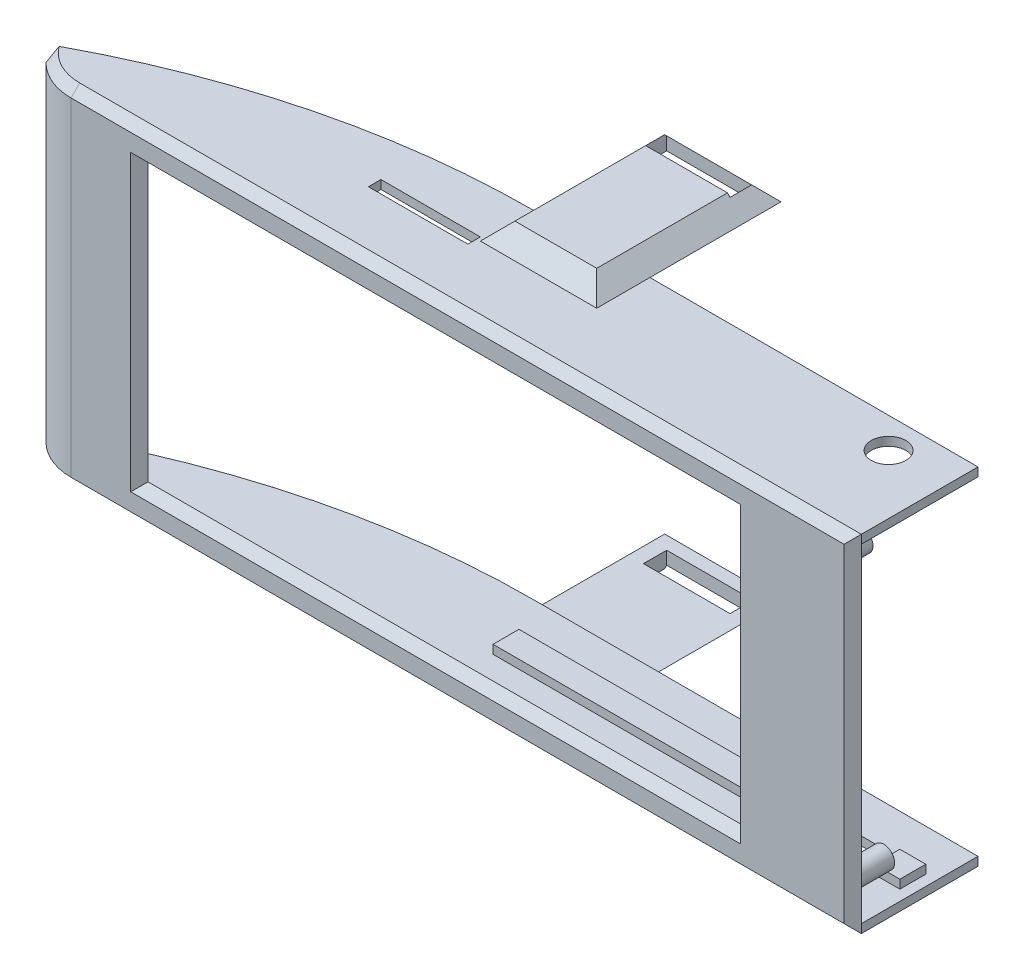
SolidWorks part; units mm, degrees
material "PLA"
ref_plane "Front Plane" through (0, 0, 0) normal (0, 0, 1) x (1, 0, 0)
ref_plane "Top Plane" through (0, 0, 0) normal (0, 1, 0) x (1, 0, 0)
ref_plane "Right Plane" through (0, 0, 0) normal (1, 0, 0) x (0, 0, -1)
sketch "Sketch1" plane through (101441.594, 0, 0) normal (0, 0, 1) x (-1, 0, 0)
  line L1 (101382.549, 35) -> (101451.049, 35)
  line L2 (101382.549, 35) -> (101382.549, 3)
  line L3 (101382.549, 3) -> (101451.049, 3)
  line L8 (101458.949, 39) -> (101368.549, 39)
  line L9 (101458.949, -1) -> (101458.949, 39)
  line L10 (101368.549, -1) -> (101458.949, -1)
  line L11 (101368.549, 39) -> (101368.549, -1)
  line L12 (101451.049, 35) -> (101451.049, 3)
  dimension "D2" = 68.5
  dimension "D3" = 14
  dimension "D4" = 4
  dimension "D5" = 4
  dimension "D6" = 90.4
  dimension "D1" = 40
extrude "Boss-Extrude1" add sketch "Sketch1" along normal blind 1
sketch "Sketch2" plane through (0, 0, 0) normal (0, 0, -1) x (-1, 0, 0)
  line L0 (-73.0451, 1) -> (17.3549, 1) construction
  line L1 (17.3549, -39) -> (-73.0451, -39) construction
  line L2 (-73.0451, -39) -> (-73.0451, 1) construction
  circle A0 centre (-70.1451, -2.5) radius 1.25
  circle A1 centre (-70.1451, -35.5) radius 1.25
  circle A2 centre (14.3549, -2.5) radius 1.25
  circle A3 centre (14.3549, -35.5) radius 1.25
  dimension "D4" = 2.5
  dimension "D1" = 3.5
  dimension "D2" = 3.5
  dimension "D3" = 2.9
  dimension "D5" = 2
extrude "Boss-Extrude2" add sketch "Sketch2" along normal blind 3
sketch "Sketch3" plane through (0, 1, 0) normal (0, 1, 0) x (1, 0, 0)
  line L0 (73.0451, 0) -> (-17.3549, 0) construction
  line L1 (-17.3549, -1) -> (-17.3549, 0) construction
  line L2 (-22.3549, 2.6834) -> (-22.3549, 1.101)
  line L3 (-17.3549, -1) -> (-17.3549, 0)
  arc A0 (-17.3549, 0) -> (-22.3549, 2.6834) centre (-17.3549, 6) cw
  arc A1 (-17.3549, -1) -> (-22.3549, 1.101) centre (-17.3549, 6) cw
  arc A3 (-17.3549, -1) -> (-23.1883, 2.1306) centre (-17.3549, 6) cw construction
  dimension "D1" = 6
  dimension "D2" = 5
extrude "Boss-Extrude3" add sketch "Sketch3" against normal through all separate body
chamfer "Chamfer1" distance 1 angle 45 2 edges at (-20.0667, 1, 0.4534) (-20.0667, -39, 0.4534)
chamfer "Chamfer2" distance 1 angle 45 7 edges at (24.7951, -3, 1) (-9.4549, -19, 1) (24.7951, -35, 1) (59.0451, -19, 1) (27.8451, -39, 1) (73.0451, -19, 1) (27.8451, 1, 1)
ref_plane "Plane1" through (0, -39, 0) normal (0, 1, 0) x (1, 0, 0)
ref_plane "Plane2" through (0, 1, 0) normal (0, 1, 0) x (1, 0, 0)
sketch "Sketch6" plane through (0, 1, 0) normal (0, 1, 0) x (1, 0, 0)
  line L0 (73.0451, 0) -> (-17.3549, 0) construction
  line L1 (71.8188, 0) -> (61.8388, 0)
  line L2 (71.8188, 0) -> (71.8188, 13.9185)
  line L3 (71.8188, 13.9185) -> (61.8388, 13.9185)
  line L4 (61.8388, 0) -> (61.8388, 13.9185)
  line L5 (29.764, 0) -> (-0.962, 0)
  line L6 (29.764, 0) -> (29.764, 11.5588)
  line L7 (29.764, 11.5588) -> (-0.962, 11.5588)
  line L8 (-0.962, 0) -> (-0.962, 11.5588)
  line L10 (19.6612, 5.9892) -> (7.4739, 5.9892)
  line L11 (19.6612, 5.9892) -> (19.6612, 7.9655)
  line L12 (19.6612, 7.9655) -> (7.4739, 7.9655)
  line L13 (7.4739, 5.9892) -> (7.4739, 7.9655)
  circle A0 centre (66.8561, 9.9375) radius 1.9758
extrude "Boss-Extrude4" add sketch "Sketch6" against normal blind 1
sketch "Sketch8" plane through (0, 0, 0) normal (0, -1, 0) x (1, 0, 0)
  line L0 (29.764, 0) -> (29.764, -11.5588) construction
  line L1 (29.764, -8.6788) -> (24.764, -8.6788)
  line L2 (29.764, -8.6788) -> (29.764, -5.6788)
  line L3 (29.764, -5.6788) -> (24.764, -5.6788)
  line L4 (24.764, -8.6788) -> (24.764, -5.6788)
  line L5 (29.764, -11.5588) -> (-0.962, -11.5588) construction
  dimension "D1" = 5.88
  dimension "D2" = 3
  dimension "D3" = 5
extrude "Boss-Extrude6" add sketch "Sketch8" along normal blind 1
sketch "Sketch9" plane through (0, -39, 0) normal (0, 1, 0) x (1, 0, 0)
  line L1 (67.2061, 8.8062) -> (63.1589, 8.8062)
  line L2 (67.2061, 8.8062) -> (67.2061, 6.8122)
  line L3 (67.2061, 6.8122) -> (63.1589, 6.8122)
  line L4 (29.764, 0) -> (29.764, 11.5588)
  line L5 (29.764, 11.5588) -> (-0.962, 11.5588)
  line L6 (-0.962, 11.5588) -> (-0.962, 0)
  line L7 (-0.962, 0) -> (29.764, 0)
  line L8 (29.764, 0) -> (29.764, 11.5588)
  line L9 (29.764, 11.5588) -> (-0.962, 11.5588)
  line L10 (-0.962, 11.5588) -> (-0.962, 0)
  line L11 (-0.962, 0) -> (29.764, 0)
  line L12 (71.8188, 0) -> (71.8188, 13.9185)
  line L13 (61.8388, 0) -> (71.8188, 0)
  line L14 (61.8388, 13.9185) -> (61.8388, 0)
  line L15 (71.8188, 13.9185) -> (61.8388, 13.9185)
  line L16 (71.8188, 0) -> (71.8188, 13.9185)
  line L17 (61.8388, 0) -> (71.8188, 0)
  line L18 (61.8388, 13.9185) -> (61.8388, 0)
  line L19 (71.8188, 13.9185) -> (61.8388, 13.9185)
  line L20 (63.1589, 8.8062) -> (63.1589, 6.8122)
  dimension "D1" = 0
  dimension "D2" = 0
extrude "Boss-Extrude7" add sketch "Sketch9" along normal blind 1
sketch "Sketch10" plane through (0, -38, 0) normal (0, 1, 0) x (1, 0, 0)
  line L0 (71.8188, 0) -> (71.8188, 13.9185) construction
  line L1 (71.8188, 5.6785) -> (68.8188, 5.6785)
  line L2 (71.8188, 5.6785) -> (71.8188, 8.6785)
  line L3 (71.8188, 8.6785) -> (68.8188, 8.6785)
  line L4 (29.764, 5.6788) -> (29.764, 8.6788)
  line L5 (24.764, 5.6788) -> (29.764, 5.6788)
  line L6 (24.764, 8.6788) -> (24.764, 5.6788)
  line L7 (29.764, 8.6788) -> (24.764, 8.6788)
  line L8 (29.764, 5.6788) -> (29.764, 8.6788)
  line L9 (24.764, 5.6788) -> (29.764, 5.6788)
  line L10 (24.764, 8.6788) -> (24.764, 5.6788)
  line L11 (29.764, 8.6788) -> (24.764, 8.6788)
  line L12 (68.8188, 5.6785) -> (68.8188, 8.6785)
  line L13 (71.8188, 13.9185) -> (61.8388, 13.9185) construction
  dimension "D2" = 8.24
  dimension "D3" = 3
  dimension "D4" = 3
  dimension "D1" = 0
extrude "Boss-Extrude8" add sketch "Sketch10" along normal blind 1
sketch "Sketch11" plane through (29.764, 0, 0) normal (1, 0, 0) x (0, 0, -1)
  line L8 (11.5588, 1) -> (0, 1)
  line L9 (0, 1) -> (0, 0)
  line L10 (0, 0) -> (5.6788, 0)
  line L11 (5.6788, 0) -> (5.6788, -1)
  line L12 (5.6788, -1) -> (8.6788, -1)
  line L13 (8.6788, -1) -> (8.6788, 0)
  line L14 (8.6788, 0) -> (11.5588, 0)
  line L15 (11.5588, 0) -> (11.5588, 1)
  line L16 (11.5588, 1) -> (0, 1)
  line L17 (0, 1) -> (0, 0)
  line L18 (0, 0) -> (5.6788, 0)
  line L19 (5.6788, 0) -> (5.6788, -1)
  line L20 (5.6788, -1) -> (8.6788, -1)
  line L21 (8.6788, -1) -> (8.6788, 0)
  line L22 (8.6788, 0) -> (11.5588, 0)
  line L23 (11.5588, 0) -> (11.5588, 1)
  dimension "D1" = 0
extrude "Boss-Extrude9" add sketch "Sketch11" along normal up to vertex (32.0748 mm away) up to point (61.8388, 1, 0)
sketch "Sketch12" plane through (29.764, 0, 0) normal (1, 0, 0) x (0, 0, -1)
  line L8 (0, -39) -> (11.5588, -39)
  line L9 (11.5588, -39) -> (11.5588, -38)
  line L10 (11.5588, -38) -> (8.6788, -38)
  line L11 (8.6788, -38) -> (8.6788, -37)
  line L12 (8.6788, -37) -> (5.6788, -37)
  line L13 (5.6788, -37) -> (5.6788, -38)
  line L14 (5.6788, -38) -> (0, -38)
  line L15 (0, -38) -> (0, -39)
  line L16 (0, -39) -> (11.5588, -39)
  line L17 (11.5588, -39) -> (11.5588, -38)
  line L18 (11.5588, -38) -> (8.6788, -38)
  line L19 (8.6788, -38) -> (8.6788, -37)
  line L20 (8.6788, -37) -> (5.6788, -37)
  line L21 (5.6788, -37) -> (5.6788, -38)
  line L22 (5.6788, -38) -> (0, -38)
  line L23 (0, -38) -> (0, -39)
  dimension "D1" = 0
extrude "Boss-Extrude10" add sketch "Sketch12" along normal up to vertex (32.0748 mm away) up to point (61.8388, -39, -13.9185)
sketch "Sketch13" plane through (0, -39, 0) normal (0, -1, 0) x (1, 0, 0)
  line L1 (-22.3549, -5.5334) -> (-22.3549, -2.6834) construction
  line L2 (-17.3549, 0) -> (-0.962, 0) construction
  line L3 (-17.3549, 0) -> (-0.962, 0)
  line L4 (-0.962, -11.5588) -> (-0.962, 0) construction
  line L5 (-0.962, -11.5588) -> (-0.962, 0)
  arc A0 (-22.3549, -5.5334) -> (-0.962, -11.5588) centre (15.2842, 87.1127) ccw
  arc A2 (-17.3549, 0) -> (-22.3549, -2.6834) centre (-17.3549, -6) ccw construction
  arc A3 (-17.3549, 0) -> (-22.3549, -2.6834) centre (-17.3549, -6) ccw
  arc A4 (-22.3549, -2.6834) -> (-23.2939, -5.1463) centre (-17.3549, -6) ccw
  arc A5 (-22.3549, -5.5334) -> (-23.2939, -5.1463) centre (15.2842, 87.1127) cw
  dimension "D1" = 100
  dimension "D2" = 2.85
extrude "Boss-Extrude11" add sketch "Sketch13" against normal up to surface (1 mm away) up to face at (54.6666, -38, -7.9669)
sketch "Sketch14" plane through (0, 1, 0) normal (0, 1, 0) x (1, 0, 0)
  line L0 (-0.962, 0) -> (-17.3549, 0)
  line L1 (-0.962, 11.5588) -> (-0.962, 0)
  arc A0 (-22.3549, 2.6834) -> (-17.3549, 0) centre (-17.3549, 6) ccw construction
  arc A1 (-23.2939, 5.1463) -> (-22.3549, 2.6834) centre (-17.3549, 6) ccw construction
  arc A2 (-0.962, 11.5588) -> (-23.2939, 5.1463) centre (15.2842, -87.1127) ccw construction
  arc A3 (-22.3549, 2.6834) -> (-17.3549, 0) centre (-17.3549, 6) ccw
  arc A4 (-23.2939, 5.1463) -> (-22.3549, 2.6834) centre (-17.3549, 6) ccw
  arc A5 (-0.962, 11.5588) -> (-23.2939, 5.1463) centre (15.2842, -87.1127) ccw
extrude "Boss-Extrude12" add sketch "Sketch14" against normal up to surface (1 mm away) up to face at (43.3014, 0, -7.1788)
sketch "Sketch15" plane through (0, 1, 0) normal (0, 1, 0) x (1, 0, 0)
  line L0 (61.8388, 13.9185) -> (61.8388, 11.5588) construction
  line L1 (61.8388, 13.9185) -> (61.8388, 11.5588)
  line L4 (61.8388, 13.9185) -> (-0.962, 11.5588)
  line L5 (-0.962, 11.5588) -> (61.8388, 11.5588)
extrude "Boss-Extrude13" add sketch "Sketch15" against normal up to surface (1 mm away) up to face at (43.3014, 0, -7.1788)
sketch "Sketch16" plane through (0, -39, 0) normal (0, -1, 0) x (1, 0, 0)
  line L0 (-0.962, -11.5588) -> (61.8388, -13.9185) construction
  line L1 (-0.962, -11.5588) -> (61.8388, -13.9185)
  line L2 (61.8388, -13.9185) -> (61.8388, -11.5588) construction
  line L3 (61.8388, -11.5588) -> (-0.962, -11.5588) construction
  line L4 (61.8388, -13.9185) -> (61.8388, -11.5588)
  line L5 (61.8388, -11.5588) -> (-0.962, -11.5588)
extrude "Boss-Extrude14" add sketch "Sketch16" against normal up to surface (1 mm away) up to face at (40.3303, -38, -7.289)
sketch "Sketch18" plane through (0, 1, 0) normal (0, 1, 0) x (1, 0, 0)
  line L4 (71.8188, 0) -> (71.8188, 13.9185)
  line L5 (71.8188, 13.9185) -> (61.8388, 13.9185)
  line L6 (61.8388, 13.9185) -> (-0.962, 11.5588)
  line L7 (-17.3549, 0) -> (71.8188, 0)
  line L8 (71.8188, 0) -> (71.8188, 13.9185)
  line L9 (71.8188, 13.9185) -> (61.8388, 13.9185)
  line L10 (61.8388, 13.9185) -> (-0.962, 11.5588)
  line L11 (-17.3549, 0) -> (71.8188, 0)
  arc A3 (-0.962, 11.5588) -> (-23.2939, 5.1463) centre (15.2842, -87.1127) ccw
  arc A4 (-23.2939, 5.1463) -> (-22.3549, 2.6834) centre (-17.3549, 6) ccw
  arc A5 (-22.3549, 2.6834) -> (-17.3549, 0) centre (-17.3549, 6) ccw
  arc A6 (-0.962, 11.5588) -> (-23.2939, 5.1463) centre (15.2842, -87.1127) ccw
  arc A7 (-23.2939, 5.1463) -> (-22.3549, 2.6834) centre (-17.3549, 6) ccw
  arc A8 (-22.3549, 2.6834) -> (-17.3549, 0) centre (-17.3549, 6) ccw
  dimension "D1" = 0
extrude "Cut-Extrude1" cut sketch "Sketch18" against normal blind 1
sketch "Sketch17" plane through (0, 1, 0) normal (0, 1, 0) x (1, 0, 0)
  line L0 (73.0451, 13.49) -> (73.0451, 0)
  line L2 (73.0477, 13.49) -> (21.6451, 13.49)
  line L4 (73.0451, 0) -> (-17.3549, 0)
  line L5 (71.8188, 0) -> (71.8188, 13.9185) construction
  line L11 (19.6612, 5.9892) -> (19.6612, 7.9655)
  line L12 (7.4739, 5.9892) -> (19.6612, 5.9892)
  line L13 (7.4739, 7.9655) -> (7.4739, 5.9892)
  line L14 (19.6612, 7.9655) -> (7.4739, 7.9655)
  arc A1 (21.6451, 13.49) -> (-22.211, 2.476) centre (21.6451, -79.331) ccw
  arc A3 (-22.211, 2.476) -> (-17.3549, 0) centre (-17.3549, 6) ccw
  circle A5 centre (66.8561, 9.9375) radius 1.9758
  dimension "D1" = 92.821
  dimension "D5" = 3.9517
  dimension "D6" = 6
  dimension "D2" = 1.2289
  dimension "D3" = 50.1737
  dimension "D4" = 94.0298
  dimension "D7" = 7.4739
  dimension "D8" = 19.6612
  dimension "D9" = 66.8561
  dimension "D10" = 17.3549
  dimension "D11" = 5.9892
  dimension "D12" = 7.9655
  dimension "D13" = 9.9375
extrude "Boss-Extrude15" add sketch "Sketch17" against normal blind 1 contours A1 A3 L4 L0 L2 A5 L14 L11 L12 L13 region at (30.6754, 1, -6.2222)
sketch "Sketch19" plane through (0, -39, 0) normal (0, -1, 0) x (1, 0, 0)
  line L4 (-0.962, -11.5588) -> (61.8388, -13.9185)
  line L5 (61.8388, -13.9185) -> (71.8188, -13.9185)
  line L6 (71.8188, -13.9185) -> (71.8188, 0)
  line L7 (71.8188, 0) -> (-17.3549, 0)
  line L8 (-0.962, -11.5588) -> (61.8388, -13.9185)
  line L9 (61.8388, -13.9185) -> (71.8188, -13.9185)
  line L10 (71.8188, -13.9185) -> (71.8188, 0)
  line L11 (71.8188, 0) -> (-17.3549, 0)
  arc A3 (-17.3549, 0) -> (-22.3549, -2.6834) centre (-17.3549, -6) ccw
  arc A4 (-22.3549, -2.6834) -> (-23.2939, -5.1463) centre (-17.3549, -6) ccw
  arc A5 (-23.2939, -5.1463) -> (-0.962, -11.5588) centre (15.2842, 87.1127) ccw
  arc A6 (-17.3549, 0) -> (-22.3549, -2.6834) centre (-17.3549, -6) ccw
  arc A7 (-22.3549, -2.6834) -> (-23.2939, -5.1463) centre (-17.3549, -6) ccw
  arc A8 (-23.2939, -5.1463) -> (-0.962, -11.5588) centre (15.2842, 87.1127) ccw
  dimension "D1" = 0
extrude "Cut-Extrude2" cut sketch "Sketch19" against normal blind 1
sketch "Sketch20" plane through (0, -38, 0) normal (0, -1, 0) x (1, 0, 0)
  line L3 (21.6451, -13.49) -> (73.0451, -13.49)
  line L4 (73.0451, -13.49) -> (73.0451, 0)
  line L5 (73.0451, 0) -> (-17.3549, 0)
  line L6 (21.6451, -13.49) -> (73.0451, -13.49)
  line L7 (73.0451, -13.49) -> (73.0451, 0)
  line L8 (73.0451, 0) -> (-17.3549, 0)
  line L14 (67.6677, -6.28) -> (62.6677, -6.28)
  line L15 (62.6677, -6.28) -> (62.6677, -9.28)
  line L16 (62.6677, -9.28) -> (67.6677, -9.28)
  line L17 (67.6677, -9.28) -> (67.6677, -6.28)
  arc A2 (-22.211, -2.476) -> (21.6451, -13.49) centre (21.6451, 79.331) ccw
  arc A3 (-17.3549, 0) -> (-22.211, -2.476) centre (-17.3549, -6) ccw
  arc A4 (-22.211, -2.476) -> (21.6451, -13.49) centre (21.6451, 79.331) ccw
  arc A5 (-17.3549, 0) -> (-22.211, -2.476) centre (-17.3549, -6) ccw
  dimension "D1" = 0
extrude "Boss-Extrude16" add sketch "Sketch20" along normal blind 1
sketch "Sketch21" plane through (0, -39, 0) normal (0, -1, 0) x (1, 0, 0)
  line L0 (-22.211, -2.476) -> (-22.3549, -1.101)
  line L1 (-22.3549, -1.101) -> (-22.3549, -2.6834)
  arc A0 (-22.211, -2.476) -> (-22.3549, -2.6834) centre (-17.3549, -6) ccw construction
  arc A1 (-22.211, -2.476) -> (-22.3549, -2.6834) centre (-17.3549, -6) ccw
extrude "Cut-Extrude3" cut sketch "Sketch21" against normal through all both and the other way through all
sketch "Sketch22" plane through (0, 0, -3) normal (0, 0, -1) x (-1, 0, 0)
  circle A1 centre (-70.1451, -35.5) radius 1.25
  circle A2 centre (-70.1451, -35.5) radius 1.25
  dimension "D1" = 0
extrude "Boss-Extrude17" add sketch "Sketch22" along normal blind 2.5
sketch "Sketch23" plane through (0, 1, 0) normal (0, 1, 0) x (1, 0, 0)
  line L0 (7.4739, 7.9655) -> (7.4739, 5.9892) construction
  line L1 (19.6612, 5.9892) -> (19.6612, 7.9655) construction
  line L2 (7.4739, 5.9892) -> (19.6612, 5.9892) construction
  line L3 (19.6612, 7.9655) -> (7.4739, 7.9655) construction
  line L4 (7.4739, 7.9655) -> (7.4739, 5.9892)
  line L5 (19.6612, 5.9892) -> (19.6612, 7.9655)
  line L6 (7.4739, 5.9892) -> (19.6612, 5.9892)
  line L7 (19.6612, 7.9655) -> (7.4739, 7.9655)
  circle A0 centre (66.8561, 9.9375) radius 1.9758 construction
  circle A1 centre (66.8561, 9.9375) radius 1.9758
extrude "Boss-Extrude18" add sketch "Sketch23" against normal up to surface (1 mm away) up to face at (43.3014, 0, -7.1788)
sketch "Sketch24" plane through (0, -39, 0) normal (0, -1, 0) x (1, 0, 0)
  line L0 (62.6677, -6.28) -> (62.6677, -9.28) construction
  line L1 (62.6677, -9.28) -> (67.6677, -9.28) construction
  line L2 (67.6677, -9.28) -> (67.6677, -6.28) construction
  line L3 (67.6677, -6.28) -> (62.6677, -6.28) construction
  line L4 (62.6677, -6.28) -> (62.6677, -9.28)
  line L5 (62.6677, -9.28) -> (67.6677, -9.28)
  line L6 (67.6677, -9.28) -> (67.6677, -6.28)
  line L7 (67.6677, -6.28) -> (62.6677, -6.28)
extrude "Boss-Extrude19" add sketch "Sketch24" against normal up to surface (1 mm away) up to face at (65.1677, -38, -7.78)
sketch "Sketch25" plane through (0, -39, 0) normal (0, -1, 0) x (1, 0, 0)
  line L4 (62.8337, -6.78) -> (62.8337, -8.78)
  line L5 (66.8337, -6.78) -> (62.8337, -6.78)
  line L6 (66.8337, -8.78) -> (66.8337, -6.78)
  line L7 (62.8337, -8.78) -> (66.8337, -8.78)
extrude "Cut-Extrude4" cut sketch "Sketch25" against normal up to surface (1 mm away) up to face at (25.4382, -38, -6.3168)
sketch "Sketch26" plane through (0, 1, 0) normal (0, 1, 0) x (1, 0, 0)
  line L8 (9.9839, 6.55) -> (10.7769, 6.55) construction
  line L9 (10.7769, 7.5) -> (9.9839, 7.5) construction
  line L10 (9.9839, 7.5) -> (9.9839, 6.55) construction
  line L11 (20.9835, 7.5) -> (20.9835, 6.55) construction
  line L12 (10.7769, 6.55) -> (20.1766, 6.55) construction
  line L13 (20.1766, 6.55) -> (20.9835, 6.55) construction
  line L14 (20.9835, 7.5) -> (20.1766, 7.5) construction
  line L15 (10.7769, 7.5) -> (20.1766, 7.5) construction
  line L16 (9.7339, 7.75) -> (9.7339, 6.3)
  line L17 (9.7339, 6.3) -> (10.7769, 6.3)
  line L18 (10.7769, 6.3) -> (20.1766, 6.3)
  line L19 (20.1766, 6.3) -> (21.2335, 6.3)
  line L20 (21.2335, 7.75) -> (21.2335, 6.3)
  line L21 (21.2335, 7.75) -> (20.1766, 7.75)
  line L22 (10.7769, 7.75) -> (20.1766, 7.75)
  line L23 (10.7769, 7.75) -> (9.7339, 7.75)
  circle A3 centre (66.2227, 9.9656) radius 2
  dimension "D2" = 0.25
extrude "Cut-Extrude5" cut sketch "Sketch26" against normal up to surface (1 mm away) contours L22 L23 L16 L17 L18 L19 L20 L21 | A3 region at (15.4837, 1, -7.025) region at (66.2227, 1, -9.9656) up to face at (43.3014, 0, -7.1788)
sketch "Sketch27" plane through (0, 1, 0) normal (0, 1, 0) x (1, 0, 0)
  line L0 (35.1041, 13.49) -> (35.1041, 7.3346)
  line L1 (21.6451, 13.49) -> (35.1041, 13.49) construction
  line L2 (21.6451, 13.49) -> (21.6451, 28.6497)
  line L3 (21.6451, 28.6497) -> (35.1041, 28.6497)
  line L4 (35.1041, 13.49) -> (35.1041, 28.6497)
  line L5 (35.1041, 7.3346) -> (21.6451, 7.3346)
  line L6 (21.6451, 7.3346) -> (21.6451, 13.49)
  line L8 (33.4052, 27.1416) -> (23.3878, 27.1416)
  line L9 (33.4052, 27.1416) -> (33.4052, 24.4566)
  line L10 (33.4052, 24.4566) -> (23.3878, 24.4566)
  line L11 (23.3878, 27.1416) -> (23.3878, 24.4566)
extrude "Boss-Extrude20" add sketch "Sketch27" along normal blind 2
sketch "Sketch28" plane through (0, -39, 0) normal (0, -1, 0) x (1, 0, 0)
  line L0 (23.3878, -27.1416) -> (23.3878, -24.4566) construction
  line L1 (33.4052, -24.4566) -> (33.4052, -27.1416) construction
  line L2 (23.3878, -24.4566) -> (33.4052, -24.4566) construction
  line L3 (33.4052, -27.1416) -> (23.3878, -27.1416) construction
  line L4 (21.6451, -7.3346) -> (21.6451, -28.6497)
  line L5 (35.1041, -7.3346) -> (21.6451, -7.3346)
  line L6 (35.1041, -28.6497) -> (35.1041, -7.3346)
  line L7 (21.6451, -28.6497) -> (35.1041, -28.6497)
  line L8 (21.6451, -7.3346) -> (21.6451, -28.6497)
  line L9 (35.1041, -7.3346) -> (21.6451, -7.3346)
  line L10 (35.1041, -28.6497) -> (35.1041, -7.3346)
  line L11 (21.6451, -28.6497) -> (35.1041, -28.6497)
  line L12 (23.3878, -27.1416) -> (23.3878, -24.4566)
  line L13 (33.4052, -24.4566) -> (33.4052, -27.1416)
  line L14 (23.3878, -24.4566) -> (33.4052, -24.4566)
  line L15 (33.4052, -27.1416) -> (23.3878, -27.1416)
  dimension "D1" = 0
extrude "Boss-Extrude21" add sketch "Sketch28" along normal blind 2
chamfer "Chamfer3" distance 2 angle 45 8 edges at (28.3746, -41, -7.3346) (35.1041, -41, -17.9921) (21.6451, -41, -17.9921) (28.3746, -41, -28.6497) (28.3746, 3, -28.6497) (21.6451, 3, -17.9921) (28.3746, 3, -7.3346) (35.1041, 3, -17.9921)
